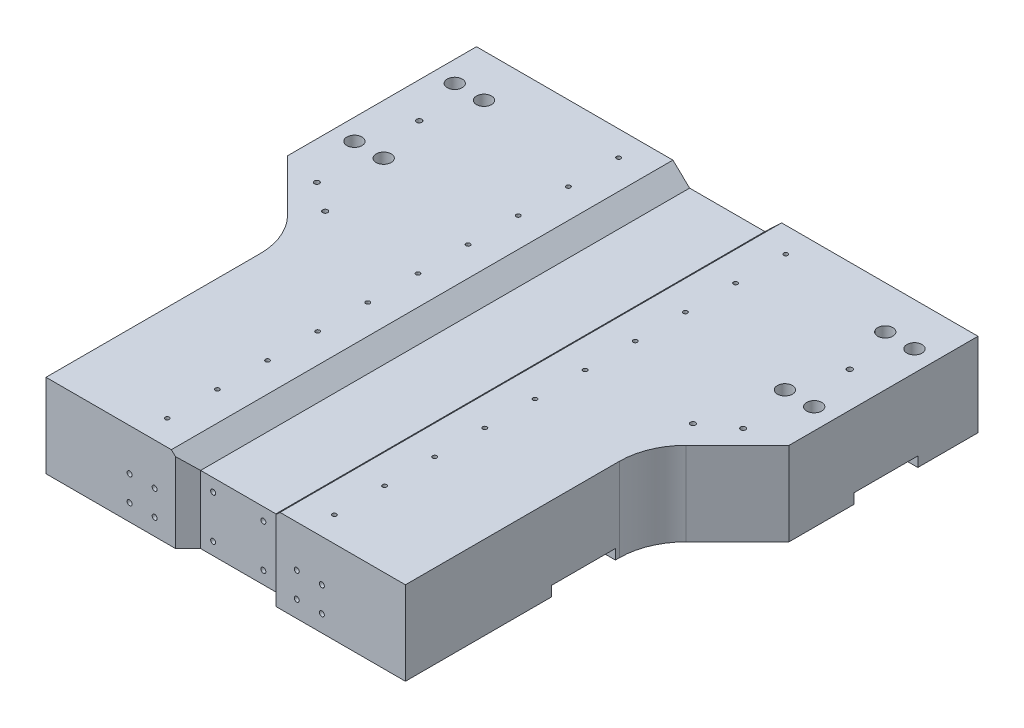
SolidWorks part; units mm, degrees
ref_plane "Front Plane" through (0, 0, 0) normal (0, 0, 1) x (1, 0, 0)
ref_plane "Top Plane" through (0, 0, 0) normal (0, 1, 0) x (1, 0, 0)
ref_plane "Right Plane" through (0, 0, 0) normal (1, 0, 0) x (0, 0, -1)
sketch "Sketch1" plane through (0, 0, 0) normal (0, 1, 0) x (1, 0, 0)
  line L1 (-300, 300) -> (300, 300)
  line L2 (-300, 300) -> (-300, -300)
  line L3 (-300, -300) -> (300, -300)
  line L4 (300, 300) -> (300, -300)
  line L5 (0, -300) -> (0, 300) construction
  line L6 (-300, 0) -> (300, 0) construction
  point P0 (0, 0)
  dimension "D1" = 600
extrude "Boss-Extrude1" add sketch "Sketch1" along normal blind 100
sketch "Sketch2" plane through (0, 100, 0) normal (0, 1, 0) x (1, 0, 0)
  line L0 (-300, -300) -> (-220, -300)
  line L9 (-300, -300) -> (300, -300) construction
  line L11 (300, -300) -> (220, -300)
  line L13 (-300, 300) -> (-300, -300) construction
  line L15 (-300, -300) -> (-300, 60)
  line L16 (300, -300) -> (300, 60)
  line L38 (-300, 60) -> (-300, 74)
  line L41 (300, 60) -> (300, 74)
  line L45 (-220, 74) -> (-300, 74)
  line L48 (220, 74) -> (300, 74)
  line L49 (-220, 74) -> (-215, 74)
  line L50 (-215, 74) -> (-215, -300)
  line L51 (-215, -300) -> (-220, -300)
  line L52 (220, 74) -> (215, 74)
  line L53 (215, 74) -> (215, -300)
  line L54 (215, -300) -> (220, -300)
extrude "Cut-Extrude1" cut sketch "Sketch2" against normal through all
chamfer "Chamfer5" distance 85 angle 45 2 edges at (-215, 50, -74) (215, 50, -74)
sketch "Sketch3" plane through (0, 0, 300) normal (0, 0, 1) x (1, 0, 0)
  line L0 (-35, 81) -> (-45, 81)
  line L2 (35, 81) -> (45, 81)
  line L4 (0, 81) -> (35, 81)
  line L8 (0, 81) -> (-35, 81)
  line L10 (-45, 100) -> (45, 100)
  line L13 (-215, 100) -> (215, 100) construction
  line L14 (-65, 100) -> (-45, 100)
  line L17 (45, 100) -> (65, 100)
  line L22 (-45, 81) -> (-65, 100)
  line L23 (45, 81) -> (65, 100)
extrude "Cut-Extrude2" cut sketch "Sketch3" against normal through all
sketch "Sketch9" plane through (0, 100, 0) normal (0, 1, 0) x (1, 0, 0)
  circle A0 centre (275, 129) radius 9.017
  circle A1 centre (240, 129) radius 9.017
  circle A3 centre (240, 249) radius 9.017
  circle A5 centre (275, 249) radius 9.017
  circle A6 centre (-275, 129) radius 9.017
  circle A7 centre (-240, 249) radius 9.017
  circle A8 centre (-275, 249) radius 9.017
  circle A11 centre (-240, 129) radius 9.017
  circle A12 centre (240, 189) radius 9.017 [skipped]
  circle A13 centre (275, 189) radius 9.017 [skipped]
  dimension "D1" = 2
  dimension "D2" = 3
extrude "Cut-Extrude5" cut sketch "Sketch9" against normal through all
sketch "Sketch12" plane through (0, 100, 0) normal (0, 1, 0) x (1, 0, 0)
  circle A40 centre (-100, -270) radius 2.5
  circle A41 centre (100, -270) radius 2.5
  circle A42 centre (100, -210) radius 2.5
  circle A43 centre (100, -150) radius 2.5
  circle A44 centre (100, -90) radius 2.5
  circle A45 centre (100, -30) radius 2.5
  circle A46 centre (100, 30) radius 2.5
  circle A47 centre (100, 90) radius 2.5
  circle A48 centre (100, 150) radius 2.5
  circle A49 centre (100, 210) radius 2.5
  circle A50 centre (100, 270) radius 2.5
  circle A61 centre (-100, -210) radius 2.5
  circle A62 centre (-100, -150) radius 2.5
  circle A63 centre (-100, -90) radius 2.5
  circle A64 centre (-100, -30) radius 2.5
  circle A65 centre (-100, 30) radius 2.5
  circle A66 centre (-100, 90) radius 2.5
  circle A67 centre (-100, 150) radius 2.5
  circle A68 centre (-100, 210) radius 2.5
  circle A69 centre (-100, 270) radius 2.5
  dimension "D1" = 2
  dimension "D2" = 10
extrude "Cut-Extrude7" cut sketch "Sketch12" against normal blind 30
sketch "Sketch14" plane through (0, 81, 0) normal (0, 1, 0) x (1, 0, 0)
  line L5 (-45, -300) -> (45, -300)
  line L6 (-45, -300) -> (-45, -285)
  line L11 (45, -285) -> (45, -300)
  line L15 (-45, -285) -> (45, -285)
extrude "Cut-Extrude8" cut sketch "Sketch14" against normal through all
chamfer "Chamfer3" distance 15 angle 45 2 edges at (45, 40.5, 300) (-45, 40.5, 300)
sketch "Sketch15" plane through (-300, 0, 0) normal (-1, 0, 0) x (0, 0, 1)
  line L0 (125, -0.7) -> (125, 12) construction
  line L1 (125, 12) -> (48.8, 12) construction
  line L2 (48.8, 12) -> (48.8, -0.7) construction
  line L3 (48.8, -0.7) -> (125, -0.7) construction
  line L4 (-228, 12) -> (-228, -0.7) construction
  line L5 (-228, -0.7) -> (-151.8, -0.7) construction
  line L6 (-151.8, -0.7) -> (-151.8, 12) construction
  line L7 (-151.8, 12) -> (-228, 12) construction
  line L8 (125, -0.7) -> (125, 12)
  line L9 (125, 12) -> (48.8, 12)
  line L10 (48.8, 12) -> (48.8, -0.7)
  line L11 (48.8, -0.7) -> (125, -0.7)
  line L12 (-228, 12) -> (-228, -0.7)
  line L13 (-228, -0.7) -> (-151.8, -0.7)
  line L14 (-151.8, -0.7) -> (-151.8, 12)
  line L15 (-151.8, 12) -> (-228, 12)
extrude "Cut-Extrude9" cut sketch "Sketch15" against normal through all
sketch "Sketch22" plane through (0, 0, -300) normal (0, 0, -1) x (-1, 0, 0)
  line L0 (-45, 81) -> (-45, 0)
  line L1 (-300, 0) -> (300, 0) construction
  line L2 (-45, 0) -> (45, 0)
  line L3 (45, 0) -> (45, 81)
  line L4 (45, 81) -> (-45, 81)
sketch "Sketch17" plane through (0, 0, 285) normal (0, 0, 1) x (1, 0, 0)
  line L8 (30, 66) -> (-30, 66)
  line L9 (-30, 66) -> (-30, 15)
  line L10 (-30, 15) -> (30, 15)
  line L11 (30, 15) -> (30, 66)
  line L12 (30, 66) -> (-30, 66)
  line L13 (-30, 66) -> (-30, 15)
  line L14 (-30, 15) -> (30, 15)
  line L15 (30, 15) -> (30, 66)
  dimension "D1" = 15
sketch "Sketch19" plane through (0, 0, -300) normal (0, 0, -1) x (-1, 0, 0)
  line L0 (30, 66) -> (30, 15) construction
  line L1 (30, 15) -> (-30, 15) construction
  line L2 (-30, 15) -> (-30, 66) construction
  line L3 (-30, 66) -> (30, 66) construction
  line L4 (30, 66) -> (30, 15)
  line L5 (30, 15) -> (-30, 15)
  line L6 (-30, 15) -> (-30, 66)
  line L7 (-30, 66) -> (30, 66)
sketch "Sketch20" plane through (0, 0, 300) normal (0, 0, 1) x (1, 0, 0)
  line L2 (85, 100) -> (85, 50)
  line L3 (-85, 0) -> (-85, 20)
  line L4 (-215, 100) -> (-65, 100) construction
  line L5 (-85, 100) -> (-85, 50)
  line L6 (115, 100) -> (115, 50)
  line L7 (-115, 100) -> (-115, 50)
  line L8 (0, 34.1921) -> (0, 91.6213)
  line L9 (-215, 0) -> (-60, 0) construction
  line L10 (-115, 0) -> (-115, 20)
  line L11 (85, 0) -> (85, 20)
  line L12 (115, 0) -> (115, 20)
sketch "Sketch21" plane through (0, 0, -300) normal (0, 0, -1) x (-1, 0, 0)
  line L4 (-115, 100) -> (-115, 80)
  line L5 (-85, 100) -> (-85, 80)
  line L6 (85, 100) -> (85, 80)
  line L7 (115, 100) -> (115, 80)
  line L8 (115, 0) -> (115, 20) construction
  line L9 (85, 0) -> (85, 20) construction
  line L10 (-85, 0) -> (-85, 20) construction
  line L11 (-115, 0) -> (-115, 20) construction
  line L12 (115, 0) -> (115, 20)
  line L13 (85, 0) -> (85, 20)
  line L14 (-85, 0) -> (-85, 20)
  line L15 (-115, 0) -> (-115, 20)
hole_wizard "Ø6.0mm Dowel Hole1" positions "3DSketch2" profile "Sketch18" hole size "Ø6.0" standard "ANSI Metric"
sketch3d "3DSketch2"
  point P0 (-30, 66, 285)
  point P3 (30, 66, 285)
  point P6 (30, 15, 285)
  point P9 (-30, 15, 285)
  point P13 (30, 66, -300)
  point P16 (-30, 66, -300)
  point P19 (-30, 15, -300)
  point P22 (30, 15, -300)
  point P26 (-85, 50, 300)
  point P29 (-115, 50, 300)
  point P32 (85, 50, 300)
  point P35 (115, 50, 300)
  point P38 (-115, 80, -300)
  point P41 (-85, 80, -300)
  point P44 (85, 80, -300)
  point P47 (115, 80, -300)
  point P50 (-115, 20, 300)
  point P53 (-85, 20, 300)
  point P56 (85, 20, 300)
  point P59 (115, 20, 300)
  point P62 (-115, 20, -300)
  point P65 (-85, 20, -300)
  point P68 (85, 20, -300)
  point P71 (115, 20, -300)
sketch "Sketch18" plane through (-30, 66, 285) normal (1, 0, 0) x (0, -1, 0)
  line L0 (0, 0) -> (0, 31.8026)
  line L1 (0, 31.8026) -> (3, 30)
  line L2 (3, 30) -> (3, 0)
  line L5 (3, 0) -> (0, 0)
  line L10 (0, 31.8026) -> (-3, 30) construction
  line L11 (0, -6.35) -> (0, 107.95) construction
  dimension "Hole Dia." = 6
  dimension "Hole Depth" = 30
  dimension "Drill Angle" = 118
sketch "Sketch23" plane through (0, 100, 0) normal (0, 1, 0) x (1, 0, 0)
  circle A0 centre (-257.5, 189) radius 3.175
  circle A1 centre (257.5, 189) radius 3.175
extrude "Cut-Extrude10" cut sketch "Sketch23" against normal through all
sketch "Sketch24" plane through (0, 100, 0) normal (0, 1, 0) x (1, 0, 0)
  line L0 (210, 74) -> (300, 74) construction
  line L1 (210, 74) -> (300, 74)
  line L2 (210, 74) -> (210, 4)
  line L3 (210, 39) -> (220, 39)
  line L4 (255, 74) -> (255, 64)
  line L5 (0, 0) -> (0, -82.778)
  circle A0 centre (255, 64) radius 3
  circle A1 centre (220, 39) radius 3
  circle A2 centre (-220, 39) radius 3
  circle A3 centre (-255, 64) radius 3
extrude "Cut-Extrude11" cut sketch "Sketch24" against normal blind 20 contours A3 | A2 | A0 | A1
fillet "Fillet1" radius 80 2 edges at (215, 50, 11) (-215, 50, 11)
